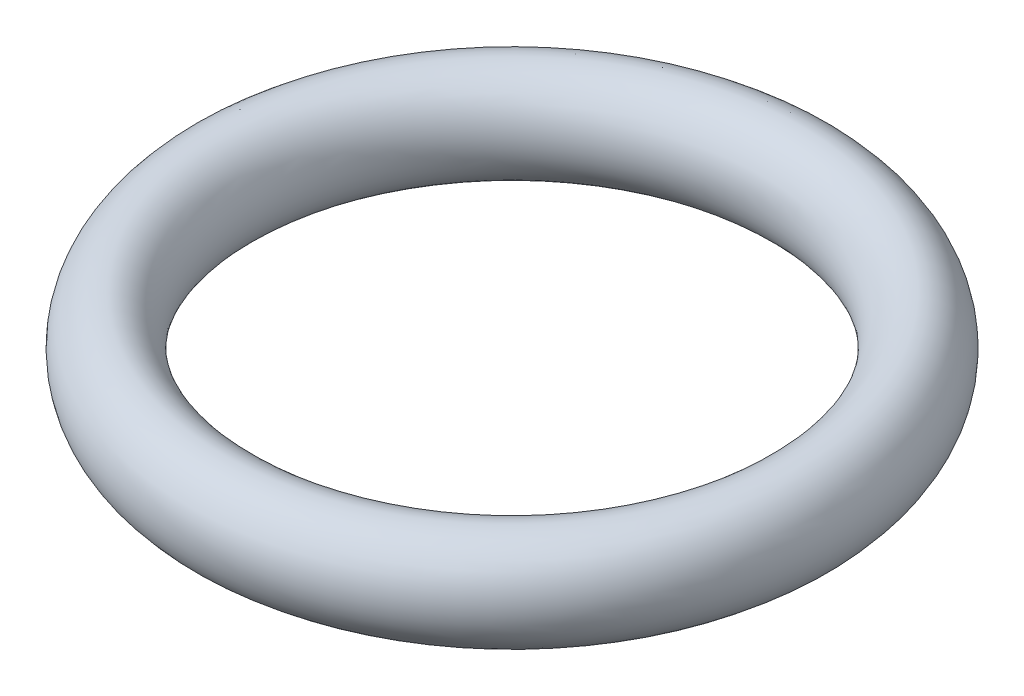
SolidWorks part; units mm, degrees
material "Rubber"
ref_plane "Front Plane" through (0, 0, 0) normal (0, 0, 1) x (1, 0, 0)
ref_plane "Top Plane" through (0, 0, 0) normal (0, 1, 0) x (1, 0, 0)
ref_plane "Right Plane" through (0, 0, 0) normal (1, 0, 0) x (0, 0, -1)
sketch "body_sketch" plane through (0, 0, 0) normal (0, 0, 1) x (1, 0, 0)
  line L0 (-5.7952, 0) -> (0, 0) construction
  line L1 (0, 1) -> (0, -1) construction
  line L2 (0, 1) -> (-5.7951, 1) construction
  line L3 (-5.7952, -1) -> (0, -1) construction
  ellipse E0 centre (-5.7952, 0) end of major axis (-5.7951, 1) minor radius 0.8548
  dimension "D1" = 6.65
  dimension "D2" = 4.9403
  dimension "D3" = 2
revolve "body" add sketch "body_sketch" angle 360 about L1
ref_plane "top_plane" through (0, 1, 0) normal (0, 1, 0) x (1, 0, 0)
ref_plane "bottom_plane" through (0, -1, 0) normal (0, 1, 0) x (1, 0, 0)
ref_axis "axis" through (0, 1, 0) along (0, -1, 0)
